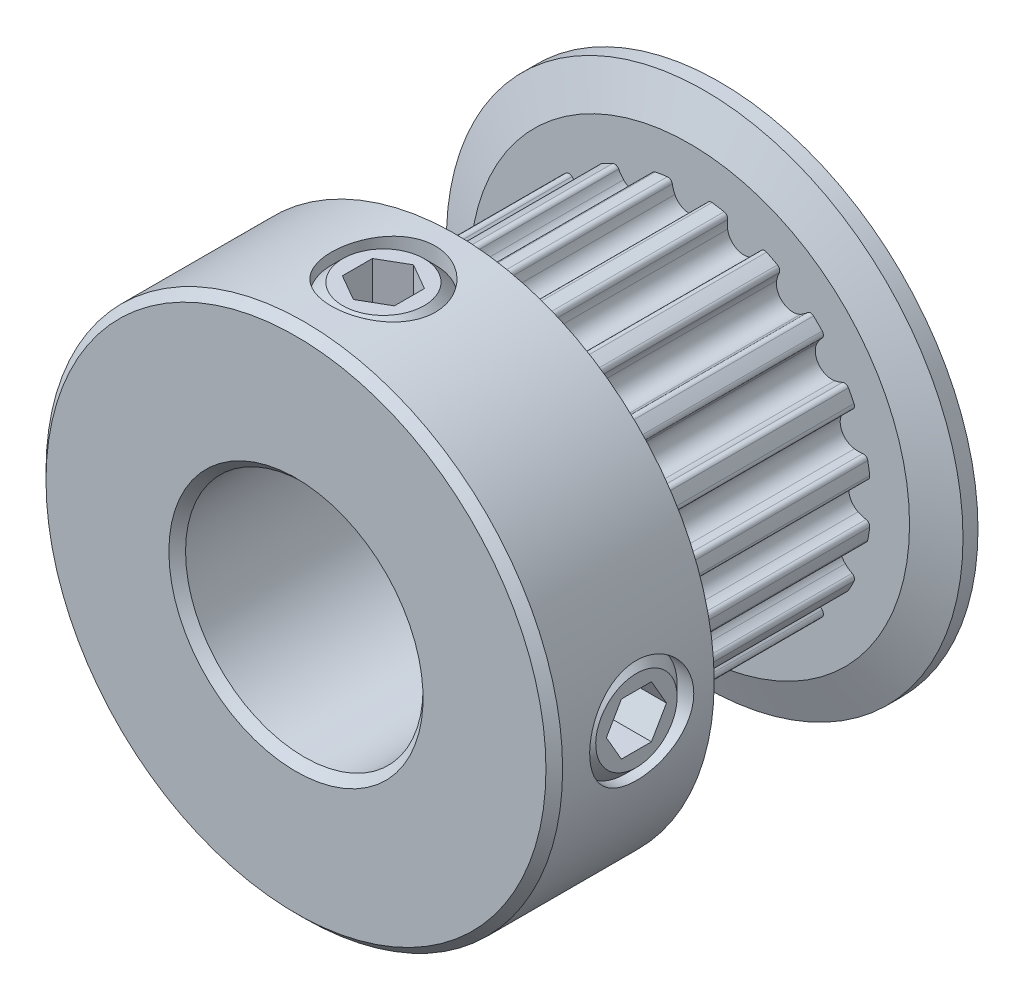
SolidWorks part; units mm, degrees
ref_plane "Front Plane" through (0, 0, 0) normal (0, 0, 1) x (1, 0, 0)
ref_plane "Top Plane" through (0, 0, 0) normal (0, 1, 0) x (1, 0, 0)
ref_plane "Right Plane" through (0, 0, 0) normal (1, 0, 0) x (0, 0, -1)
sketch "Sketch1" plane through (0, 0, 0) normal (0, 0, 1) x (1, 0, 0)
  line L1 (-1.7499, 5.3585) -> (1.7499, 5.3585) construction
  line L4 (0, 0) -> (0, 5.3585) construction
  line L5 (0, 5.3585) -> (0, 11.2095) construction
  line L6 (0, 6.3625) -> (1.9751, 6.0482) construction
  line L7 (1.9751, 6.0482) -> (2.6648, 5.8229) construction
  line L8 (1.9751, 6.0482) -> (1.7499, 5.3585) construction
  line L9 (-1.9751, 6.0482) -> (-1.7499, 5.3585) construction
  line L10 (-1.8963, 5.8067) -> (-2.841, 8.6995)
  line L11 (-2.841, 8.6995) -> (2.841, 8.6995)
  line L12 (2.841, 8.6995) -> (1.8963, 5.8067)
  circle A0 centre (0, 0) radius 6.3625 construction
  circle A1 centre (0, 0) radius 8.6995 construction
  circle A2 centre (0, 0) radius 6.1085 construction
  arc A3 (-0.4989, 5.6703) -> (0.4989, 5.6703) centre (0, 5.9135) ccw
  arc A4 (-0.4989, 5.6703) -> (-0.5855, 5.9387) centre (0.4, 6.1085) cw
  arc A5 (-1.8963, 5.8067) -> (-0.7518, 6.0621) centre (0, 0) cw
  arc A6 (-0.5855, 5.9387) -> (-0.7518, 6.0621) centre (-0.7333, 5.9132) ccw
  arc A7 (1.8963, 5.8067) -> (0.7518, 6.0621) centre (0, 0) ccw
  arc A8 (0.5855, 5.9387) -> (0.7518, 6.0621) centre (0.7333, 5.9132) cw
  arc A9 (0.4989, 5.6703) -> (0.5855, 5.9387) centre (-0.4, 6.1085) ccw
  point P6 (0, 20.9083)
  point P11 (0, 6.3625)
  point P13 (0, 8.6995)
  point P14 (0, 6.1085)
  dimension "D1" = 9.6989
  dimension "D2" = 4.847
sketch "Sketch2" plane through (0, 0, 0) normal (1, 0, 0) x (0, 0, -1)
  line L0 (-7.135, 4) -> (7.135, 4)
  line L1 (-7.135, 4) -> (-7.135, 8.6995)
  line L2 (-1.75, 8.6995) -> (-7.135, 8.6995)
  line L3 (-2.255, 4) -> (-2.255, 8.6995) construction
  line L4 (-2.255, 8.6995) -> (-1.245, 8.6995) construction
  line L5 (-1.245, 8.6995) -> (-1.245, 6.1085) construction
  line L6 (-1.245, 6.1085) -> (6.125, 6.1085)
  line L7 (6.125, 6.1085) -> (6.125, 8.6995) construction
  line L8 (6.125, 8.6995) -> (7.135, 8.6995) construction
  line L9 (7.135, 8.6995) -> (7.135, 4)
  line L10 (-7.135, 0) -> (7.135, 0) construction
  line L11 (6.63, 8.6995) -> (6.125, 7.404)
  line L12 (-1.245, 7.404) -> (-1.75, 8.6995)
  line L14 (-1.245, 7.404) -> (-1.245, 6.1085)
  line L15 (6.125, 6.1085) -> (6.125, 7.404)
  line L16 (6.63, 8.6995) -> (7.135, 8.6995)
  arc A0 (-1.245, 7.404) -> (-1.75, 8.6995) centre (-3.1592, 7.404) ccw construction
  arc A1 (6.125, 7.404) -> (6.63, 8.6995) centre (8.0392, 7.404) cw construction
  point P12 (-1.245, 7.404)
  point P14 (-1.75, 8.6995)
  point P20 (6.125, 7.404)
  point P21 (6.63, 8.6995)
  point P25 (6.125, 0)
  point P26 (-1.245, 0)
  dimension "OA" = 14.27
  dimension "Bore" = 8
  dimension "Outside Width" = 8.38
  dimension "Inside Width" = 7.37
revolve "Revolve1" add sketch "Sketch2" angle 360 mid plane about L10
sketch "Sketch3" plane through (0, 0, 0) normal (0, 0, 1) x (1, 0, 0)
  line L6 (2.841, 8.6995) -> (-2.841, 8.6995)
  line L7 (1.8963, 5.8067) -> (2.841, 8.6995)
  line L8 (-2.841, 8.6995) -> (-1.8963, 5.8067)
  line L9 (2.841, 8.6995) -> (-2.841, 8.6995)
  line L10 (1.8963, 5.8067) -> (2.841, 8.6995)
  line L11 (-2.841, 8.6995) -> (-1.8963, 5.8067)
  arc A8 (1.8963, 5.8067) -> (0.7518, 6.0621) centre (0, 0) ccw
  arc A9 (0.7518, 6.0621) -> (0.5855, 5.9387) centre (0.7333, 5.9132) ccw
  arc A10 (0.4989, 5.6703) -> (0.5855, 5.9387) centre (-0.4, 6.1085) ccw
  arc A11 (-0.4989, 5.6703) -> (0.4989, 5.6703) centre (0, 5.9135) ccw
  arc A12 (-0.5855, 5.9387) -> (-0.4989, 5.6703) centre (0.4, 6.1085) ccw
  arc A13 (-0.5855, 5.9387) -> (-0.7518, 6.0621) centre (-0.7333, 5.9132) ccw
  arc A14 (-0.7518, 6.0621) -> (-1.8963, 5.8067) centre (0, 0) ccw
  arc A15 (1.8963, 5.8067) -> (0.7518, 6.0621) centre (0, 0) ccw
  arc A16 (0.7518, 6.0621) -> (0.5855, 5.9387) centre (0.7333, 5.9132) ccw
  arc A17 (0.4989, 5.6703) -> (0.5855, 5.9387) centre (-0.4, 6.1085) ccw
  arc A18 (-0.4989, 5.6703) -> (0.4989, 5.6703) centre (0, 5.9135) ccw
  arc A19 (-0.5855, 5.9387) -> (-0.4989, 5.6703) centre (0.4, 6.1085) ccw
  arc A20 (-0.5855, 5.9387) -> (-0.7518, 6.0621) centre (-0.7333, 5.9132) ccw
  arc A21 (-0.7518, 6.0621) -> (-1.8963, 5.8067) centre (0, 0) ccw
  dimension "D1" = 0
extrude "Cut-Extrude1" cut sketch "Sketch3" against normal up to vertex (6.125 mm away) from vertex up to point (0, 6.1085, -6.125) starting at point (0, 6.1085, 1.245)
pattern_circular "CirPattern1" count 20 over 360 about axis through (0, 0, 7.135) along (0, 0, 1) of "Cut-Extrude1"
sketch "Sketch4" plane through (0, 0, 0) normal (1, 0, 0) x (0, -1, 0)
  line L0 (0, -1.245) -> (0, -7.135) construction
  line L1 (-4, -7.135) -> (4, -7.135) construction
  line L2 (7.404, -1.245) -> (-7.404, -1.245) construction
  circle A0 centre (0, -4.19) radius 1.7526
extrude "Cut-Extrude2" cut sketch "Sketch4" along normal through all
ref_plane "Plane1" through (0, 0, 4.19) normal (0, 0, 1) x (1, 0, 0)
sketch "Sketch5" plane through (0, 0, 4.19) normal (0, 0, 1) x (1, 0, 0)
  line L0 (0, 0) -> (0, 8.6995) construction
  line L1 (4, -1.3716) -> (4, 0)
  line L2 (4.381, -1.7526) -> (8.1401, -1.7526)
  line L3 (4, 0) -> (8.6995, 0) construction
  line L4 (4, 0) -> (8.5211, 0)
  line L5 (8.5211, 0) -> (8.5211, -1.3716)
  line L6 (4.381, -1.7526) -> (4, -1.3716)
  line L7 (8.5211, -1.3716) -> (8.1401, -1.7526)
  circle A0 centre (0, 0) radius 8.6995 construction
  circle A1 centre (0, 0) radius 4 construction
  point P2 (4, -1.7526)
  point P11 (8.5211, -1.7526)
revolve "Revolve2" add sketch "Sketch5" angle 360 mid plane about L4
sketch "Sketch6" plane through (8.5211, 5.3841, 0) normal (-1, 0, 0) x (0, -1, 0)
  line L1 (5.3841, 5.2019) -> (4.5078, 4.6959)
  line L2 (4.5078, 4.6959) -> (4.5078, 3.6841)
  line L3 (4.5078, 3.6841) -> (5.3841, 3.1781)
  line L4 (5.3841, 3.1781) -> (6.2604, 3.6841)
  line L5 (6.2604, 3.6841) -> (6.2604, 4.6959)
  line L6 (6.2604, 4.6959) -> (5.3841, 5.2019)
  circle A0 centre (5.3841, 4.19) radius 0.8763 construction
  dimension "D1" = 1.7526
extrude "Cut-Extrude3" cut sketch "Sketch6" along normal blind 1.3144
pattern_circular "CirPattern3" count 2 every 90 about axis through (0, 0, 7.135) along (0, 0, 1) of "Cut-Extrude2", "Revolve2", "Cut-Extrude3"
chamfer "Chamfer1" distance 0.2807 angle 45 2 edges at (4, 0, 7.135) (8.6995, 0, 7.135)
ref_axis "Center Axis 1" through (0, 0, -7.135) along (0, 0, 1)
ref_plane "Contact Plane 1" through (0, 0, 7.135) normal (0, 0, 1) x (1, 0, 0)
ref_plane "Contact Plane 2" through (0, 0, -7.135) normal (0, 0, -1) x (-1, 0, 0)
equation "\"D2@Sketch1\"= \"D1@Sketch1\" / 2"
equation "\"D1@Sketch6\" = \"Set Screw@Sketch4\" / 2"
equation "\"D1@Cut-Extrude3\" = \"D1@Sketch6\"*.75"
